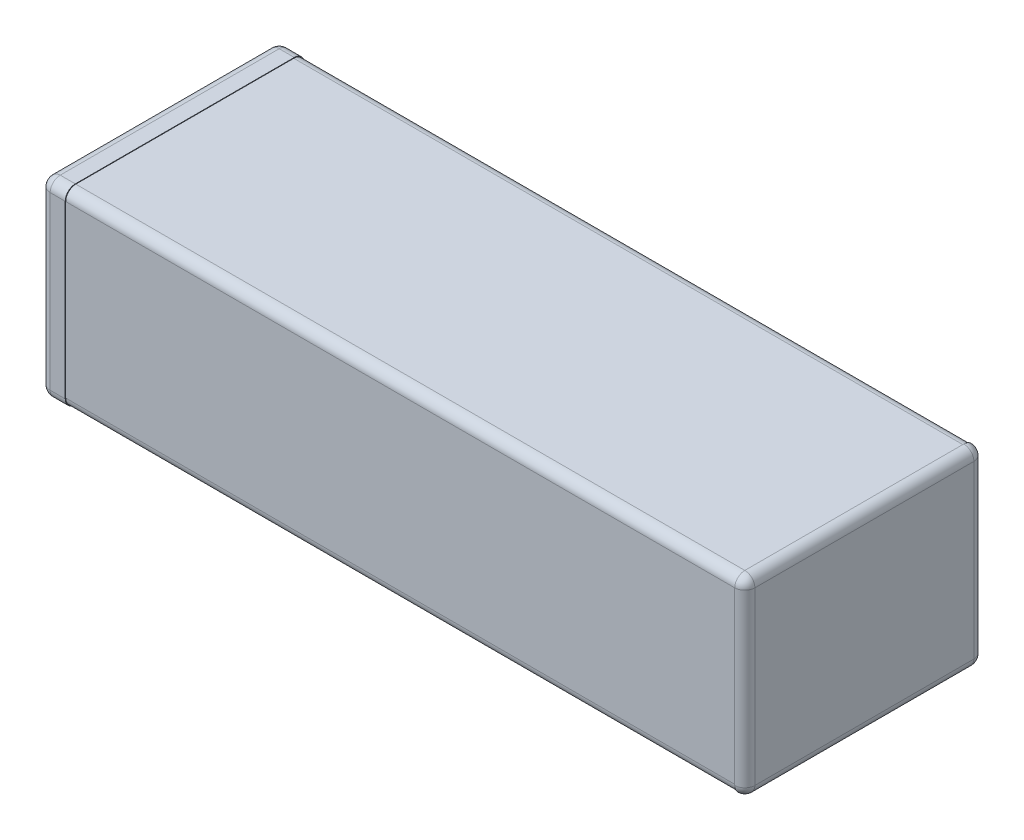
SolidWorks part; units mm, degrees
ref_plane "Front Plane" through (0, 0, 0) normal (0, 0, 1) x (1, 0, 0)
ref_plane "Top Plane" through (0, 0, 0) normal (0, 1, 0) x (1, 0, 0)
ref_plane "Right Plane" through (0, 0, 0) normal (1, 0, 0) x (0, 0, -1)
sketch "Sketch1" plane through (0, 0, 0) normal (0, 1, 0) x (1, 0, 0)
  line L1 (70, 23.75) -> (-70, 23.75)
  line L2 (70, 23.75) -> (70, -23.75)
  line L3 (70, -23.75) -> (-70, -23.75)
  line L4 (-70, 23.75) -> (-70, -23.75)
  line L5 (70, 23.75) -> (-70, -23.75) construction
  line L6 (70, -23.75) -> (-70, 23.75) construction
  point P0 (0, 0)
  dimension "D1" = 47.5
  dimension "D2" = 140
extrude "Boss-Extrude1" add sketch "Sketch1" along normal mid plane 38
sketch "Sketch3" plane through (0, 19, 0) normal (0, 1, 0) x (1, 0, 0)
  line L0 (70, 23.75) -> (-70, 23.75) construction
  line L1 (-65, 23.75) -> (68, 23.75)
  line L2 (-65, 23.75) -> (-65, -23.75)
  line L3 (-65, -23.75) -> (68, -23.75)
  line L4 (68, 23.75) -> (68, -23.75)
  line L5 (-70, -23.75) -> (70, -23.75) construction
  line L6 (-70, 23.75) -> (-70, -23.75) construction
  line L7 (70, -23.75) -> (70, 23.75) construction
  dimension "D1" = 5
  dimension "D2" = 2
extrude "Cut-Extrude1" cut sketch "Sketch3" against normal blind 0.1
mirror "Mirror1" about plane through (0, 0, 0) normal (0, 1, 0) of "Cut-Extrude1"
sketch "Sketch4" plane through (0, 0, 23.75) normal (0, 0, 1) x (1, 0, 0)
  line L1 (-65, 18.9) -> (68, 18.9)
  line L2 (-65, 18.9) -> (-65, -18.9)
  line L3 (-65, -18.9) -> (68, -18.9)
  line L4 (68, 18.9) -> (68, -18.9)
extrude "Cut-Extrude2" cut sketch "Sketch4" against normal blind 0.1
mirror "Mirror2" about plane through (0, 0, 0) normal (0, 0, 1) of "Cut-Extrude2"
sketch "Sketch7" plane through (0, -18.9, 0) normal (0, -1, 0) x (1, 0, 0)
  text T0 "7200\r\n" font "Century Gothic" height in points 72
extrude "Cut-Extrude3" cut sketch "Sketch7" against normal blind 0.1
sketch "Sketch8" plane through (0, -18.9, 0) normal (0, -1, 0) x (1, 0, 0)
  text T0 "MAH" font "Century Gothic" height in points 20
extrude "Cut-Extrude4" cut sketch "Sketch8" against normal blind 0.1
sketch "Sketch9" plane through (0, -18.9, 0) normal (0, -1, 0) x (1, 0, 0)
  text T0 "LIPO 11.1V 120C" font "Century Gothic" height in points 20
extrude "Cut-Extrude5" cut sketch "Sketch9" against normal blind 0.1
fillet "Fillet2" radius 2 16 edges at (-70, 0, -23.75) (-70, 19, 0) (-70, 0, 23.75) (-70, -19, 0) (70, 0, 23.75) (70, 19, 0) (70, 0, -23.75) (70, -19, 0) (1.5, 18.9, -23.65) (1.5, -18.9, -23.65) (1.5, 18.9, 23.65) (1.5, -18.9, 23.65) (-67.5, 19, -23.75) (-67.5, 19, 23.75) (-67.5, -19, 23.75) (-67.5, -19, -23.75)
